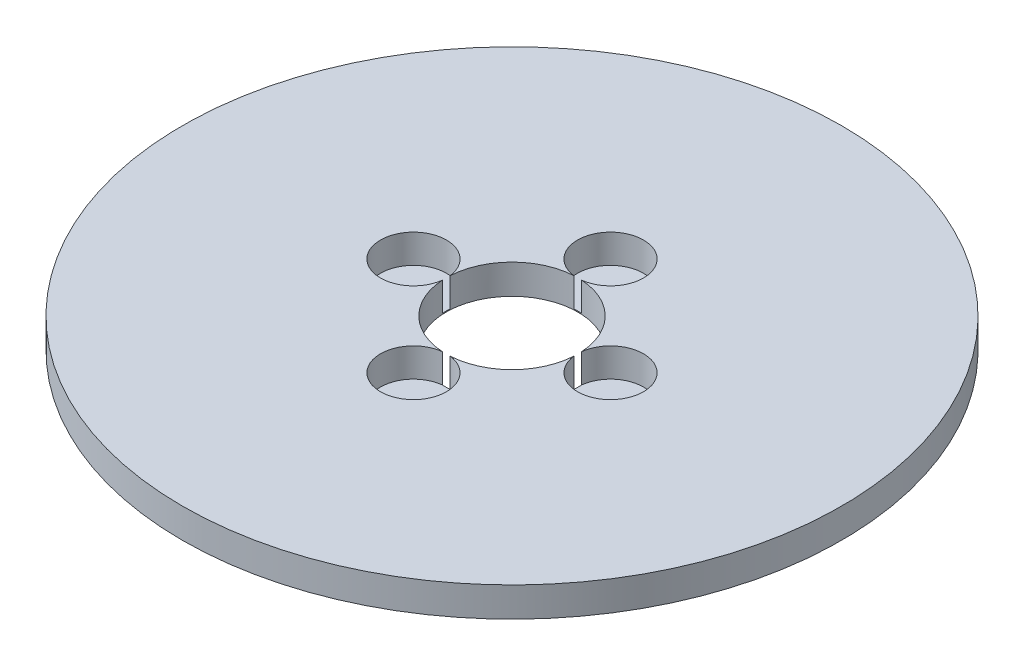
SolidWorks part; units mm, degrees
ref_plane "Front Plane" through (0, 0, 0) normal (0, 0, 1) x (1, 0, 0)
ref_plane "Top Plane" through (0, 0, 0) normal (0, 1, 0) x (1, 0, 0)
ref_plane "Right Plane" through (0, 0, 0) normal (1, 0, 0) x (0, 0, -1)
sketch "Sketch1" plane through (0, 0, 0) normal (0, 1, 0) x (1, 0, 0)
  circle A0 centre (0, 0) radius 100
  dimension "FLANGE_OD" = 200
extrude "Boss-Extrude1" add sketch "Sketch1" along normal blind 9
sketch "Sketch2" plane through (0, 0, 0) normal (0, 1, 0) x (1, 0, 0)
  circle A0 centre (0, 0) radius 20
  dimension "BORE_D" = 40
extrude "Cut-Extrude1" cut sketch "Sketch2" along normal through all
sketch "Sketch3" plane through (0, 9, 0) normal (0, 1, 0) x (1, 0, 0)
  circle A0 centre (0, 0) radius 29.8952 construction
  circle A1 centre (-29.8952, 0) radius 10
  dimension "BOLT_D" = 20
  dimension "BOLT_PCD" = 59.7905
extrude "Cut-Extrude2" cut sketch "Sketch3" against normal blind 8.7449
pattern_circular "CirPattern1" count 4 over 360 about axis through (0, 0, 0) along (0, 1, 0) of "Cut-Extrude2"
